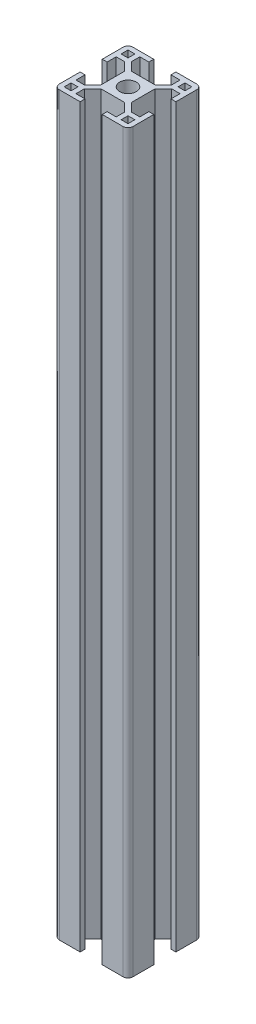
SolidWorks part; units mm, degrees
ref_plane "Front plane" through (0, 0, 0) normal (0, 0, 1) x (1, 0, 0)
ref_plane "Top plane" through (0, 0, 0) normal (0, 1, 0) x (1, 0, 0)
ref_plane "Right plane" through (0, 0, 0) normal (1, 0, 0) x (0, 0, -1)
ref_axis "Axis X" through (0, 0, 0) along (1, 0, 0)
ref_axis "Axis Y" through (0, 0, 0) along (0, 1, 0)
ref_axis "Axis Z" through (0, 0, 0) along (0, 0, 1)
sketch "Sketch1" plane through (0, 0, 0) normal (0, 1, 0) x (1, 0, 0)
  line L1 (-10, 10) -> (10, 10)
  line L2 (-10, 10) -> (-10, -10)
  line L3 (-10, -10) -> (10, -10)
  line L4 (10, 10) -> (10, -10)
  line L5 (-10, 10) -> (10, -10) construction
  line L6 (-10, -10) -> (10, 10) construction
  point P0 (0, 0)
  dimension "D2" = 20
extrude "Extrude1" add sketch "Sketch1" along normal blind 200
sketch "Sketch2" plane through (0, 200, 0) normal (0, 1, 0) x (1, 0, 0)
  line L0 (0, 0) -> (10, 0) construction
  line L1 (10, -10) -> (10, 10) construction
  line L2 (10, 10) -> (-10, 10) construction
  line L3 (8.6667, 3) -> (11.3333, 3)
  line L4 (8.6667, 3) -> (8.6667, -3) construction
  line L5 (8.6667, -3) -> (11.3333, -3)
  line L6 (11.3333, 3) -> (11.3333, -3)
  line L7 (8.6667, 3) -> (11.3333, -3) construction
  line L8 (8.6667, -3) -> (11.3333, 3) construction
  line L9 (6.8, 8.6667) -> (8.6667, 8.6667)
  line L10 (6.8, 8.6667) -> (6.8, 6.8)
  line L11 (6.8, 6.8) -> (8.6667, 6.8)
  line L12 (8.6667, 8.6667) -> (8.6667, 6.8)
  line L13 (6.8, 8.6667) -> (8.6667, 6.8) construction
  line L14 (6.8, 6.8) -> (8.6667, 8.6667) construction
  line L15 (0, 0) -> (10, 10) construction
  line L16 (8.6667, 3) -> (8.6667, 5.4667)
  line L17 (8.6667, 5.4667) -> (6.4095, 5.4667)
  line L18 (6.4095, 5.4667) -> (4.1333, 3.1905)
  line L19 (4.1333, 3.1905) -> (4.1333, -3.1905)
  line L20 (4.1333, -3.1905) -> (6.4095, -5.4667)
  line L21 (6.4095, -5.4667) -> (8.6667, -5.4667)
  line L22 (8.6667, -5.4667) -> (8.6667, -3)
  line L65 (-3.1905, 4.1333) -> (-5.4667, 6.4095)
  line L66 (-5.4667, 6.4095) -> (-5.4667, 8.6667)
  line L67 (-5.4667, 8.6667) -> (-3, 8.6667)
  line L68 (3, 11.3333) -> (-3, 11.3333)
  line L69 (-3, 8.6667) -> (-3, 11.3333)
  line L70 (3, 8.6667) -> (3, 11.3333)
  line L71 (3, 8.6667) -> (5.4667, 8.6667)
  line L72 (5.4667, 8.6667) -> (5.4667, 6.4095)
  line L73 (5.4667, 6.4095) -> (3.1905, 4.1333)
  line L74 (3.1905, 4.1333) -> (-3.1905, 4.1333)
  line L75 (0, 10) -> (0, -10) construction
  line L76 (-10, -10) -> (10, -10) construction
  line L77 (0, 0) -> (-10, 0) construction
  line L78 (-10, 10) -> (-10, -10) construction
  line L79 (8.6667, -8.6667) -> (8.6667, -6.8)
  line L80 (6.8, -6.8) -> (8.6667, -6.8)
  line L81 (6.8, -8.6667) -> (6.8, -6.8)
  line L82 (6.8, -8.6667) -> (8.6667, -8.6667)
  line L83 (-6.8, 6.8) -> (-8.6667, 6.8)
  line L84 (-8.6667, 8.6667) -> (-8.6667, 6.8)
  line L85 (-6.8, 8.6667) -> (-8.6667, 8.6667)
  line L86 (-6.8, 8.6667) -> (-6.8, 6.8)
  line L87 (-6.8, -8.6667) -> (-8.6667, -8.6667)
  line L88 (-6.8, -8.6667) -> (-6.8, -6.8)
  line L89 (-6.8, -6.8) -> (-8.6667, -6.8)
  line L90 (-8.6667, -8.6667) -> (-8.6667, -6.8)
  line L91 (-6.4095, -5.4667) -> (-8.6667, -5.4667)
  line L92 (-4.1333, -3.1905) -> (-6.4095, -5.4667)
  line L93 (-4.1333, 3.1905) -> (-4.1333, -3.1905)
  line L94 (-6.4095, 5.4667) -> (-4.1333, 3.1905)
  line L95 (-8.6667, 5.4667) -> (-6.4095, 5.4667)
  line L96 (-8.6667, 3) -> (-8.6667, 5.4667)
  line L97 (-8.6667, 3) -> (-11.3333, 3)
  line L98 (-11.3333, 3) -> (-11.3333, -3)
  line L99 (-8.6667, -3) -> (-11.3333, -3)
  line L100 (-8.6667, -5.4667) -> (-8.6667, -3)
  line L101 (3.1905, -4.1333) -> (-3.1905, -4.1333)
  line L102 (5.4667, -6.4095) -> (3.1905, -4.1333)
  line L103 (5.4667, -8.6667) -> (5.4667, -6.4095)
  line L104 (3, -8.6667) -> (5.4667, -8.6667)
  line L105 (3, -8.6667) -> (3, -11.3333)
  line L106 (3, -11.3333) -> (-3, -11.3333)
  line L107 (-3, -8.6667) -> (-3, -11.3333)
  line L108 (-5.4667, -8.6667) -> (-3, -8.6667)
  line L109 (-5.4667, -6.4095) -> (-5.4667, -8.6667)
  line L110 (-3.1905, -4.1333) -> (-5.4667, -6.4095)
  circle A0 centre (0, 0) radius 2.2667
  point P9 (7.7333, 7.7333)
  point P20 (7.5381, 5.4667)
  point P27 (10, -3)
  point P34 (-3, 10)
  point P37 (5.4667, 7.5381)
  dimension "D10" = 4.5333
  dimension "D1" = 2.6667
  dimension "D2" = 6
  dimension "D3" = 1.3333
  dimension "D4" = 1.3333
  dimension "D5" = 4.5333
  dimension "D6" = 5.4667
  dimension "D7" = 0.6667
  dimension "D8" = 1.3333
extrude "Extrude2" cut sketch "Sketch2" against normal through all
fillet "Fillet1" radius 1.3333 4 edges at (10, 100, 10) (10, 100, -10) (-10, 100, 10) (-10, 100, -10)
sketch "Эскиз1" plane through (10, 0, 0) normal (1, 0, 0) x (0, 0, -1)
  line L0 (0, 0) -> (0, 200) construction
  line L1 (3.1905, 200) -> (-3.1905, 200) construction
  line L2 (0, 100) -> (-56.213, 100) construction
  line L3 (-8.6667, 0) -> (-3, 0) construction
  circle A0 centre (0, 93) radius 2.5
  circle A1 centre (0, 107) radius 2.5
  dimension "D1" = 5
  dimension "D2" = 14
  dimension "D3" = 100
extrude "Вырез-Вытянуть1" cut sketch "Эскиз1" against normal through all
equation "\"prof_width\"= 20'Aluminium profile parameters"
equation "\"D1@Sketch1\"=\"prof_width\""
equation "\"D2@Sketch1\"=\"prof_width\""
equation "\"prof_groove\"= 6"
equation "\"prof_length\"= 200"
equation "\"D1@Extrude1\"=\"prof_length\""
equation "\"D1@Sketch2\"=\"prof_width\"/30*4"
equation "\"D2@Sketch2\"=\"prof_groove\""
equation "\"D3@Sketch2\"=\"D1@Sketch2\"/2"
equation "\"D4@Sketch2\"=\"D3@Sketch2\""
equation "\"D5@Sketch2\"=\"prof_width\"/30*6.8"
equation "\"D6@Sketch2\"=\"prof_width\"/30*8.2"
equation "\"D7@Sketch2\"=\"D3@Sketch2\"/2"
equation "\"D8@Sketch2\"=\"D3@Sketch2\""
equation "\"D10@Sketch2\"=\"prof_width\"/30*6.8"
equation "\"D1@Fillet1\"=\"prof_width\"/30*2"
